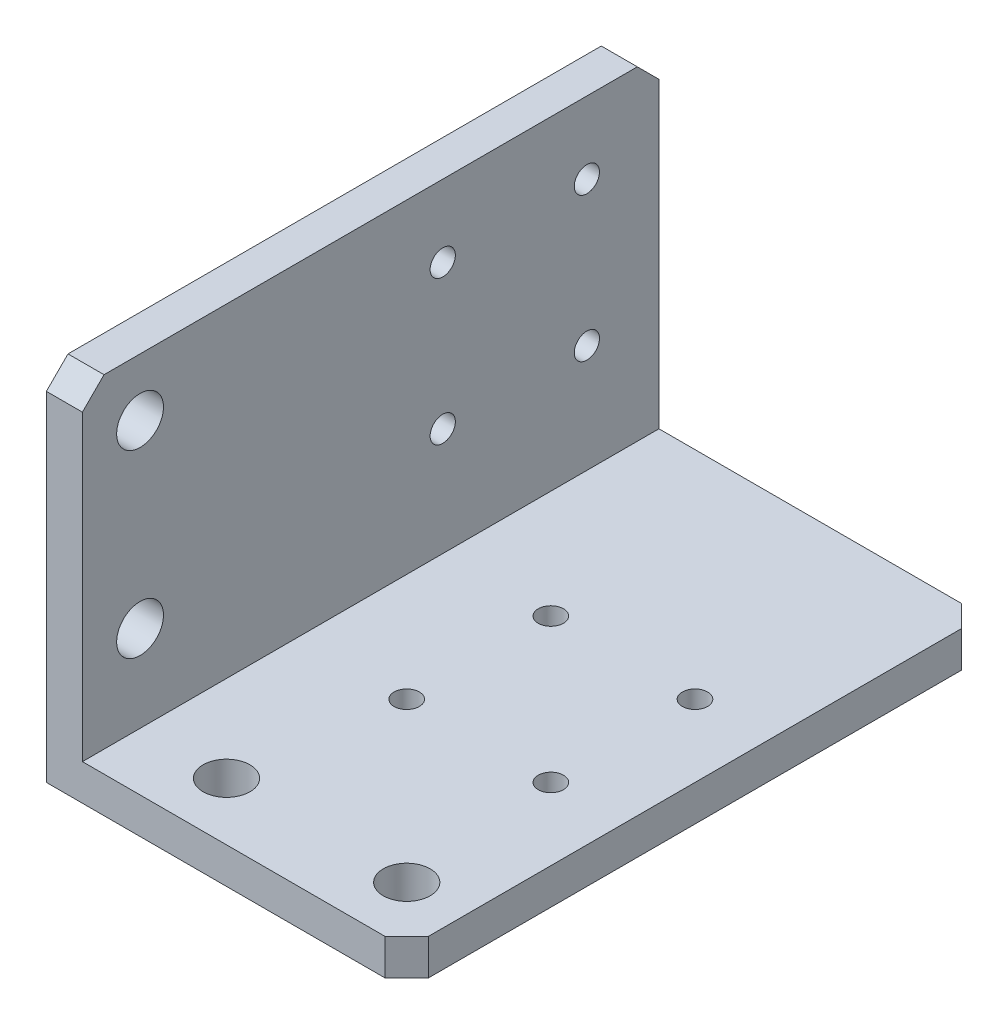
SolidWorks part; units mm, degrees
material "Lega 1060"
ref_plane "Piano frontale" through (0, 0, 0) normal (0, 0, 1) x (1, 0, 0)
ref_plane "Piano superiore" through (0, 0, 0) normal (0, 1, 0) x (1, 0, 0)
ref_plane "Piano destro" through (0, 0, 0) normal (1, 0, 0) x (0, 0, -1)
sketch "Schizzo1" plane through (0, 0, 0) normal (0, 0, 1) x (1, 0, 0)
  line L0 (0, 0) -> (0, 50)
  line L1 (0, 50) -> (5, 50)
  line L2 (5, 50) -> (5, 5)
  line L3 (5, 5) -> (50, 5)
  line L4 (50, 5) -> (50, 0)
  line L5 (50, 0) -> (0, 0)
  dimension "D1" = 5
  dimension "D2" = 5
  dimension "D3" = 50
  dimension "D4" = 50
extrude "Estrusione-Estrusione1" add sketch "Schizzo1" along normal blind 80
sketch "Schizzo2" plane through (0, 0, 0) normal (0, -1, 0) x (1, 0, 0)
  line L0 (5.4524, 72) -> (42.7933, 72) construction
  line L1 (0, 80) -> (50, 80) construction
  line L5 (50, 80) -> (50, 0) construction
  point P4 (17, 72)
  point P5 (42, 72)
  dimension "D1" = 8
  dimension "D2" = 25
  dimension "D3" = 8
sketch "Schizzo3" plane through (0, 0, 0) normal (-1, 0, 0) x (0, 0, 1)
  line L0 (72, 44.621) -> (72, 5.772) construction
  line L1 (80, 50) -> (80, 0) construction
  line L2 (80, 50) -> (0, 50) construction
  point P4 (72, 42)
  point P5 (72, 17)
  dimension "D1" = 8
  dimension "D2" = 8
  dimension "D3" = 25
hole_wizard "Foro Ø6.5 (6.5)-1" positions "Schizzo5" profile "Schizzo4" hole size "Ø6.5" standard "ISO" end condition through all
sketch "Schizzo5" plane through (0, 0, 0) normal (0, -1, 0) x (-1, 0, 0)
  point P0 (-17, -72)
  point P3 (-42, -72)
sketch "Schizzo4" plane through (17, 0, 72) normal (1, 0, 0) x (0, 0, -1)
  line L0 (0, 0) -> (0, 50)
  line L1 (0, 50) -> (3.25, 50)
  line L2 (3.25, 50) -> (3.25, 0)
  line L5 (3.25, 0) -> (0, 0)
  line L11 (0, -6.35) -> (0, 107.95) construction
  dimension "Thru Hole Dia." = 6.5
  dimension "Thru Hole Depth" = 50
hole_wizard "Foro Ø6.5 (6.5)-2" positions "Schizzo7" profile "Schizzo6" hole size "Ø6.5" standard "ISO"
sketch "Schizzo7" plane through (0, 0, 0) normal (-1, 0, 0) x (0, 0, 1)
  point P1 (72, 42)
  point P4 (72, 17)
sketch "Schizzo6" plane through (0, 42, 72) normal (0, 1, 0) x (0, 0, 1)
  line L0 (0, 0) -> (0, 6.9528)
  line L1 (0, 6.9528) -> (3.25, 5)
  line L2 (3.25, 5) -> (3.25, 0)
  line L5 (3.25, 0) -> (0, 0)
  line L10 (0, 6.9528) -> (-3.25, 5) construction
  line L11 (0, -6.35) -> (0, 107.95) construction
  dimension "Hole Dia." = 6.5
  dimension "Hole Depth" = 5
  dimension "Drill Angle" = 118
ref_plane "Piano1" through (0, 0, 40) normal (0, 0, 1) x (1, 0, 0)
sketch "Schizzo8" plane through (0, 0, 0) normal (-1, 0, 0) x (0, 0, 1)
  line L2 (80, 50) -> (80, 0) construction
  line L3 (80, 50) -> (0, 50) construction
  circle A0 centre (20, 30) radius 7
  dimension "D3" = 14
  dimension "D1" = 60
  dimension "D2" = 20
sketch "Schizzo9" plane through (0, 0, 0) normal (0, -1, 0) x (1, 0, 0)
  line L0 (50, 80) -> (50, 0) construction
  line L1 (0, 80) -> (50, 80) construction
  circle A0 centre (30, 40) radius 7
  dimension "D1" = 14
  dimension "D2" = 20
  dimension "D3" = 40
sketch "Schizzo10" plane through (0, 0, 0) normal (-1, 0, 0) x (0, 0, 1)
  line L1 (20, 42.2663) -> (20, 14.8621) construction
  line L2 (19.1906, 30.8094) -> (20, 30) construction
  circle A0 centre (10, 40) radius 1.75
  circle A1 centre (30, 40) radius 1.75
  circle A3 centre (30, 20) radius 1.75
  circle A4 centre (10, 20) radius 1.75
  circle A5 centre (20, 30) radius 7 construction
  point P20 (20, 30)
  dimension "D1" = 3.5
  dimension "D2" = 20
  dimension "D3" = 45
  dimension "D4" = 4
extrude "Taglio-Estrusione3" cut sketch "Schizzo10" against normal up to next
sketch "Schizzo11" plane through (0, 0, 0) normal (0, -1, 0) x (1, 0, 0)
  line L0 (30, 40) -> (14.4837, 40) construction
  line L1 (30, 40) -> (34.5929, 44.5929) construction
  circle A0 centre (20, 30) radius 1.75
  circle A3 centre (20, 50) radius 1.75
  circle A4 centre (40, 50) radius 1.75
  circle A5 centre (40, 30) radius 1.75
  circle A6 centre (30, 40) radius 7 construction
  point P2 (30, 40)
  point P17 (30, 40)
  dimension "D2" = 3.5
  dimension "D1" = 20
  dimension "D3" = 45
  dimension "D4" = 4
extrude "Taglio-Estrusione4" cut sketch "Schizzo11" against normal up to next
chamfer "Smusso1" distance 3 angle 45 4 edges at (2.5, 50, 0) (50, 2.5, 0) (2.5, 50, 80) (50, 2.5, 80)
